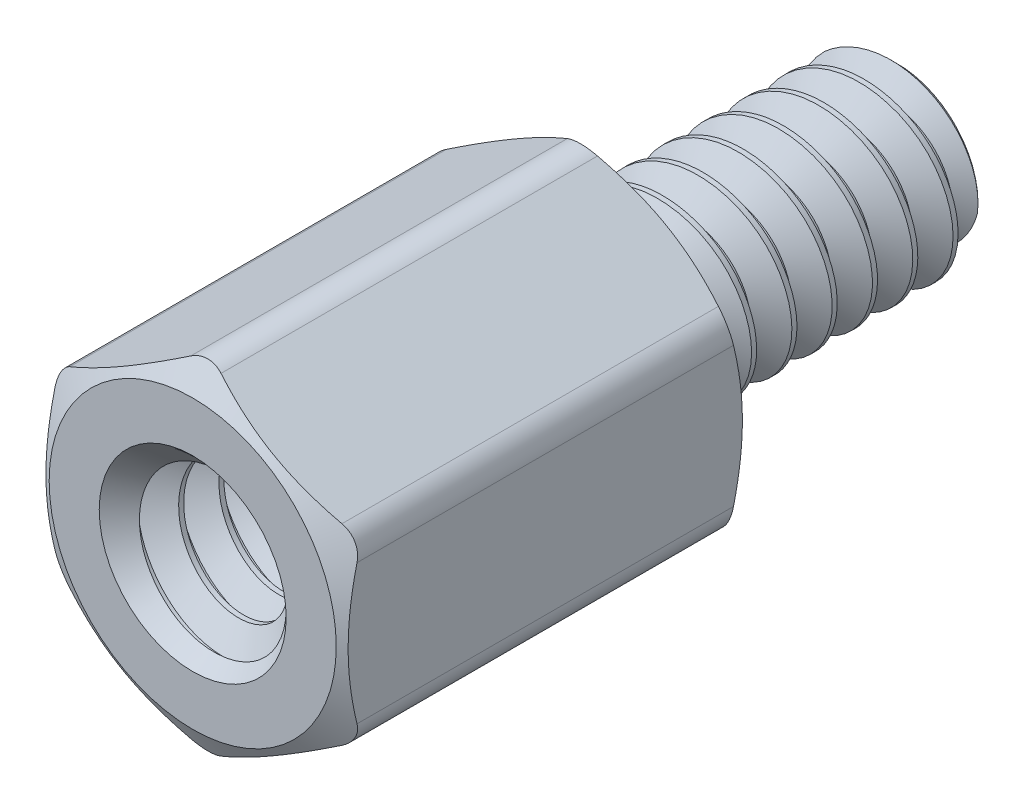
SolidWorks part; units mm, degrees
ref_plane "Front Plane" through (0, 0, 0) normal (0, 0, 1) x (1, 0, 0)
ref_plane "Top Plane" through (0, 0, 0) normal (0, 1, 0) x (1, 0, 0)
ref_plane "Right Plane" through (0, 0, 0) normal (1, 0, 0) x (0, 0, -1)
sketch "Sketch1" plane through (0, 0, 0) normal (0, 0, 1) x (1, 0, 0)
  line L1 (2.3813, 1.3748) -> (0, 2.7496)
  line L2 (0, 2.7496) -> (-2.3812, 1.3748)
  line L3 (-2.3812, 1.3748) -> (-2.3812, -1.3748)
  line L4 (-2.3812, -1.3748) -> (0, -2.7496)
  line L5 (0, -2.7496) -> (2.3813, -1.3748)
  line L6 (2.3813, -1.3748) -> (2.3813, 1.3748)
  circle A0 centre (0, 0) radius 2.3812 construction
  point P10 (0, -2.3812)
  dimension "Hex Size" = 4.7625
sketch "Sketch2" plane through (0, 0, 0) normal (1, 0, 0) x (0, 0, -1)
  line L0 (4.7625, 0) -> (-6.35, 0) construction
  line L2 (0, 1.4224) -> (0, -1.4224) construction
  line L3 (-3.175, 1.4224) -> (-3.175, -1.4224) construction
  line L4 (-6.9453, 1.4911) -> (-6.6278, 0.9412) construction
  line L5 (-6.6278, 0.9412) -> (-6.3103, 1.4911) construction
  line L6 (-6.3103, 1.4911) -> (-6.9453, 1.4911) construction
  line L7 (-6.9056, 1.4224) -> (-6.35, 1.4224) construction
  line L8 (-6.6675, 1.01) -> (-6.5881, 1.01) construction
  line L9 (-6.6278, 1.01) -> (-6.6278, 0.9412) construction
  line L10 (-6.6278, 1.4224) -> (-6.6278, 1.4911) construction
  line L11 (4.7228, 1.4911) -> (5.3578, 1.4911) construction
  line L12 (5.3578, 1.4911) -> (5.0403, 0.9412) construction
  line L13 (5.0403, 0.9412) -> (4.7228, 1.4911) construction
  line L14 (4.7625, 1.4224) -> (5.3181, 1.4224) construction
  line L15 (5.0006, 1.01) -> (5.08, 1.01) construction
  line L16 (5.0403, 1.01) -> (5.0403, 0.9412) construction
  line L17 (5.0403, 1.4224) -> (5.0403, 1.4911) construction
  line L18 (0, 2.7496) -> (-6.35, 2.7496) construction
  point P6 (0, 0)
  point P9 (-3.175, 0)
  dimension "Length" = 6.35
sketch "Sketch3" plane through (0, 0, 0) normal (1, 0, 0) x (0, 0, -1)
  line L0 (-3.175, 0) -> (4.7625, 0)
  line L1 (-3.175, 1.4224) -> (-3.175, -1.4224) construction
  line L2 (4.7625, 0) -> (4.7625, 1.2636)
  line L3 (4.7625, 1.2636) -> (4.6038, 1.4224)
  line L4 (4.6038, 1.4224) -> (0.8096, 1.4224)
  line L5 (0.8096, 1.4224) -> (0.5715, 1.01)
  line L6 (-3.175, 0) -> (-3.175, 1.2636)
  line L7 (-3.175, 1.2636) -> (-3.3338, 1.4224)
  line L8 (-3.3338, 1.4224) -> (-6.1913, 1.4224)
  line L9 (-6.1913, 1.4224) -> (-6.35, 1.5811)
  line L10 (4.6038, 0) -> (4.6038, -1.4224) construction
  line L11 (-6.35, 1.5811) -> (-6.35, 2.3812)
  line L12 (-6.35, 2.3812) -> (0, 2.3812)
  line L14 (0.5715, 1.01) -> (0.1587, 1.01)
  line L15 (0, 1.1687) -> (0, 2.3812)
  arc A0 (0, 1.1687) -> (0.1587, 1.01) centre (0.1587, 1.1687) ccw
  point P5 (-6.35, -2.3812)
  point P8 (-4.7625, -1.4224)
  point P9 (3.175, -1.4224)
  point P27 (0, 1.01)
  dimension "D4" = 0.1588
  dimension "D2" = 0.1588
  dimension "D1" = 45
  dimension "D6" = 1.5875
  dimension "D7" = 60
  dimension "D3" = 1.5875
  dimension "D5" = 0.5715
revolve "Revolve1" add sketch "Sketch3" angle 360 about L0 region at (0, 1.1264, 0.6139)
sketch "Sketch4" plane through (0, 0, 6.35) normal (0, 0, 1) x (1, 0, 0)
  line L0 (0, 2.3812) -> (0, 1.4224) construction
  line L1 (-2.3812, 1.3748) -> (-2.3812, -1.3748)
  line L2 (-2.3812, -1.3748) -> (0, -2.7496)
  line L3 (0, -2.7496) -> (2.3812, -1.3748)
  line L4 (2.3812, -1.3748) -> (2.3812, 1.3748)
  line L5 (2.3812, 1.3748) -> (0, 2.7496)
  line L6 (0, 2.7496) -> (-2.3812, 1.3748)
  circle A0 centre (0, 0) radius 2.3812 construction
  circle A1 centre (0, 0) radius 1.9018
  circle A2 centre (0, 0) radius 2.3812 construction
  point P16 (0, 1.9018)
extrude "Boss-Extrude1" add sketch "Sketch4" against normal up to surface (6.35 mm away) up to face at (0, 2.3812, 0)
sketch "Sketch5" plane through (0, 0, 6.35) normal (0, 0, 1) x (1, 0, 0)
  line L0 (-0.8159, 1.1652) -> (0.8159, -1.1652) construction
  line L1 (0, 1.4224) -> (0, -1.4224) construction
  line L3 (0, -4.9059) -> (0, 4.9059) construction
  circle A0 centre (0, 0) radius 2.2622
  point P11 (0.8159, -1.1652)
  dimension "D1" = 4.5244
  dimension "D2" = 35
extrude "Cut-Extrude1" cut sketch "Sketch5" against normal through all draft 60 flip side to cut
sketch "Sketch6" plane through (0, 0, 0) normal (0, 0, -1) x (-1, 0, 0)
  circle A0 centre (0, 0) radius 2.2622
  circle A1 centre (0, 0) radius 2.2622 construction
extrude "Cut-Extrude2" cut sketch "Sketch6" against normal through all draft 60 flip side to cut
fillet "Fillet1" radius 0.4763 6 edges at (0, 2.7496, 3.175) (-2.3812, -1.3748, 3.175) (0, -2.7496, 3.175) (2.3812, -1.3748, 3.175) (2.3812, 1.3748, 3.175) (-2.3812, 1.3748, 3.175)
sketch "Drawing1" plane through (0, 0, 0) normal (1, 0, 0) x (0, 0, -1)
  line L0 (-6.35, 1.4224) -> (-3.175, 1.4224) construction
  line L1 (-3.175, 1.4224) -> (-3.175, -1.4224) construction
  line L2 (-3.175, -1.4224) -> (-6.35, -1.4224) construction
sketch "Sketch7" plane through (0, 0, 0) normal (-1, 0, 0) x (0, 0, 1)
  line L0 (-5.0006, 1.01) -> (-5.08, 1.01)
  line L1 (-5.08, 1.01) -> (-5.338, 1.4568)
  line L2 (-5.3578, 1.4911) -> (-5.0403, 0.9412) construction
  line L3 (-5.338, 1.4568) -> (-4.7427, 1.4568)
  line L4 (-5.0403, 0.9412) -> (-4.7228, 1.4911) construction
  line L5 (-4.7427, 1.4568) -> (-5.0006, 1.01)
  line L6 (-5.0403, 1.4224) -> (-5.0403, 1.4911) construction
  point P12 (-5.0403, 1.4568)
sketch "Sketch8" plane through (0, 0, -4.7625) normal (0, 0, -1) x (-1, 0, 0)
  circle A0 centre (0, 0) radius 1.4224
curve "Helix/Spiral1" pitch 0.635 height 4.6196 radius 1.4224 centre (0, 0, -4.7625) axis (0, 0, 1) start towards (0, 1, 0)
sweep "Cut-Sweep1" cut profiles "Sketch7" path "Helix/Spiral1" align with end faces yes
sketch "Sketch9" plane through (0, 0, 3.175) normal (0, 0, 1) x (1, 0, 0)
  circle A0 centre (0, 0) radius 1.5811
extrude "Boss-Extrude2" add sketch "Sketch9" along normal up to surface (3.175 mm away) up to face at (0, 1.5811, 6.35)
sketch "Sketch10" plane through (0, 0, 0) normal (1, 0, 0) x (0, 0, -1)
  line L0 (4.7625, 0) -> (-6.35, 0) construction
  line L1 (-3.175, 1.4224) -> (-6.35, 1.4224)
  line L2 (-3.175, 1.4224) -> (-3.175, 0)
  line L3 (-3.175, 0) -> (-6.35, 0)
  line L4 (-6.35, 1.4224) -> (-6.35, 0)
revolve "Revolve2" add sketch "Sketch10" angle 360 about L0
sketch "Sketch11" plane through (0, 0, 6.35) normal (0, 0, 1) x (1, 0, 0)
  circle A0 centre (0, 0) radius 1.4224
  circle A1 centre (0, 0) radius 1.4224 construction
sketch "Sketch12" plane through (0, 0, 0) normal (1, 0, 0) x (0, 0, -1)
  line L0 (-6.6675, 1.01) -> (-6.5881, 1.01)
  line L1 (-6.5881, 1.01) -> (-6.3302, 1.4568)
  line L2 (-6.6278, 0.9412) -> (-6.3103, 1.4911) construction
  line L3 (-6.3302, 1.4568) -> (-6.9255, 1.4568)
  line L4 (-6.9453, 1.4911) -> (-6.6278, 0.9412) construction
  line L5 (-6.9255, 1.4568) -> (-6.6675, 1.01)
  line L6 (-6.6278, 1.4224) -> (-6.6278, 1.4911) construction
  point P12 (-6.6278, 1.4568)
curve "Helix/Spiral2" pitch 0.635 height 3.81 radius 1.4224 centre (0, 0, 6.35) axis (0, 0, -1) start towards (0, 1, 0)
sweep "Cut-Sweep2" cut profiles "Sketch12" path "Helix/Spiral2" align with end faces yes
combine bodies "Combine1" operation type subtract main body 113 bodies to subtract 114
sketch "Sketch13" plane through (0, 0, 6.35) normal (0, 0, 1) x (1, 0, 0)
  circle A0 centre (0, 0) radius 1.4732
  dimension "D1" = 0.0508
extrude "Cut-Extrude3" cut sketch "Sketch13" against normal through all draft 45
equation "\"Thread Pitch (B)/8@Sketch2\"=\"Thread Pitch (B)@Sketch2\"/8"
equation "\"Thread Pitch (A)/8@Sketch2\"=\"Thread Pitch (A)@Sketch2\"/8"
equation "\"D1@Sketch5\" = \"Hex Size@Sketch1\" * .95"
equation "\"D1@Fillet1\" = \"Hex Size@Sketch1\" * .1"
equation "\"D2@Sketch3\" = \"Thread Pitch (A)@Sketch2\" * .25"
equation "\"D4@Sketch3\" = \"D2@Sketch3\""
equation "\"D6@Sketch3\" = \"Thread Pitch (A)@Sketch2\" * 2.5"
equation "\"D3@Helix/Spiral1\" = \"Thread Length (A)@Sketch2\" - \"D5@Sketch3\" * .25"
equation "\"D4@Helix/Spiral1\" = \"Thread Pitch (A)@Sketch2\""
equation "\"D3@Sketch3\" = \"Thread Pitch (B)@Sketch2\" * 2.5"
equation "\"D5@Sketch3\" = \"Thread Length (A)@Sketch2\" * .12"
equation "\"D3@Helix/Spiral2\" = \"Minimum Thread Length (B)@Sketch2\" + \"Thread Pitch (B)@Sketch2\""
equation "\"D4@Helix/Spiral2\" = \"Thread Pitch (B)@Sketch2\""
